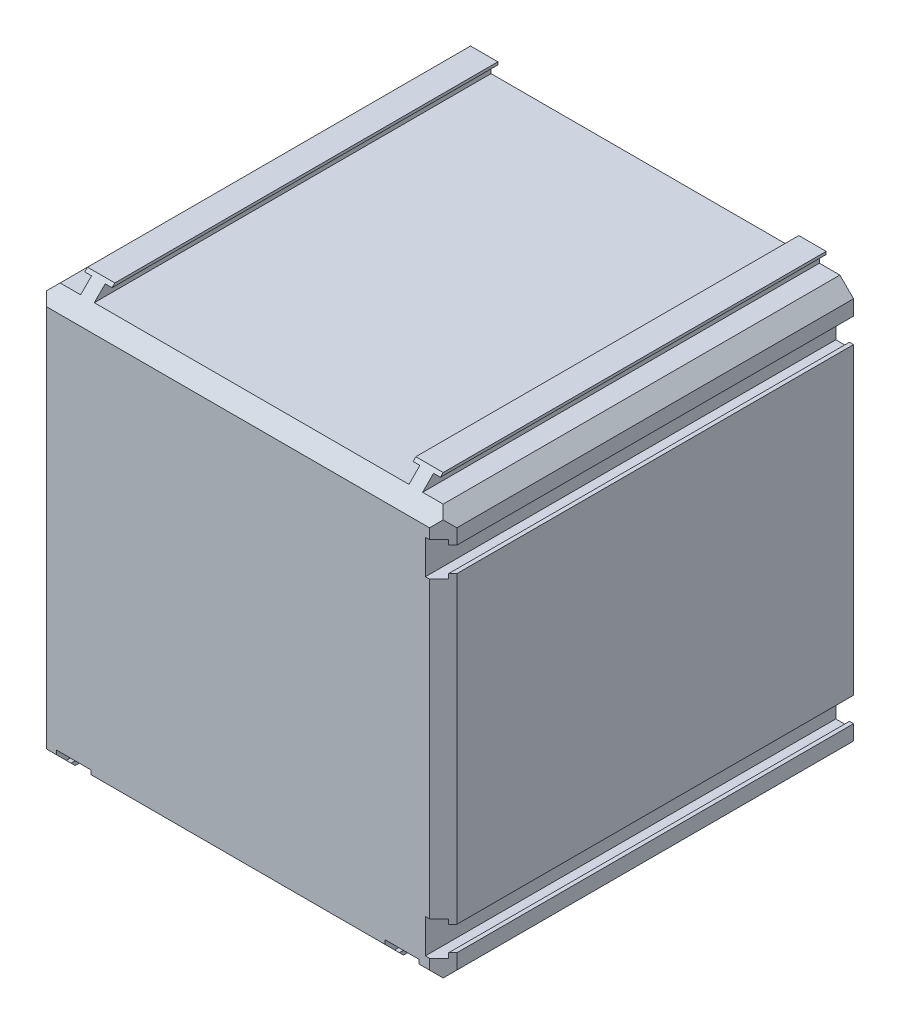
SolidWorks part; units mm, degrees
note: '?' marks a value the reader was unsure of.
ref_plane "前视基准面" through (0, 0, 0) normal (0, 0, 1) x (1, 0, 0)
ref_plane "上视基准面" through (0, 0, 0) normal (0, 1, 0) x (1, 0, 0)
ref_plane "右视基准面" through (0, 0, 0) normal (1, 0, 0) x (0, 0, -1)
sketch "草图1" plane through (0, 0, 0) normal (0, 0, 1) x (1, 0, 0)
  line L46 (-15, -15) -> (15, -15)
  line L65 (-15, -15) -> (-15, 15)
  line L74 (-15, 15) -> (15, 15)
  line L76 (15, -15) -> (15, 15)
  line L77 (-15, -15) -> (15, 15) construction
  line L78 (-15, 15) -> (15, -15) construction
  point P0 (0, 0)
  dimension "D1" = 30
  dimension "D2" = 30
extrude "凸台-拉伸1" add sketch "草图1" along normal blind 30
ref_axis "基准轴1" through (0, 0, 0) along (0, 0, -1)?
chamfer "倒角6" distance 1 angle 45 4 edges at (0, -15, 30) (15, 0, 30) (-15, 0, 30) (0, 15, 30)
sketch "草图6" plane through (0, 0, 0) normal (0, 0, 1) x (1, 0, 0)
  line L0 (-15, 0) -> (15, 0) construction
  line L1 (-12.5, 15) -> (-11.5, 15)
  line L2 (15, 15) -> (-15, 15) construction
  line L3 (-11.5, 15) -> (-11.5, 15.8)
  line L4 (-11.5, 15.8) -> (-11, 15.8)
  line L5 (-11, 15.8) -> (-11, 16)
  line L6 (-11, 16) -> (-13, 16)
  line L7 (-13, 16) -> (-13, 15.8)
  line L8 (-13, 15.8) -> (-12.5, 15.8)
  line L9 (-12.5, 15.8) -> (-12.5, 15)
  line L10 (-15, 15) -> (-15, -15) construction
  line L11 (0, 15) -> (0, -15) construction
  line L12 (-15, -15) -> (15, -15) construction
  line L13 (15, -15) -> (15, 15) construction
  line L15 (-15, 15) -> (15, 15) construction
  dimension "D1" = 2
  dimension "D2" = 0.5
  dimension "D3" = 0.5
  dimension "D4" = 0.2
  dimension "D5" = 0.2
  dimension "D6" = 0.8
  dimension "D7" = 2
  dimension "D8" = 0
extrude "凸台-拉伸3" add sketch "草图6" along normal blind 40
mirror "镜向4" about plane through (0, 0, 0) normal (1, 0, 0) of "凸台-拉伸3"
sketch "草图8" plane through (0, 0, 30) normal (0, 0, 1) x (1, 0, 0)
  line L1 (-12.9, -15) -> (-11.1, -15)
  line L2 (-11.1, -15) -> (-11.1, -14.7)
  line L3 (-11.1, -14.7) -> (-10.75, -14.7)
  line L4 (-10.75, -14.7) -> (-10.75, -13.7)
  line L5 (-10.75, -13.7) -> (-13.25, -13.7)
  line L6 (-13.25, -13.7) -> (-13.25, -14.7)
  line L7 (-13.25, -14.7) -> (-12.9, -14.7)
  line L8 (-12.9, -14.7) -> (-12.9, -15)
  line L30 (0, -15) -> (0, 15) construction
  line L31 (-15, -15) -> (15, -15) construction
  line L144 (-12, 16) -> (-12, -15) construction
  line L146 (15, -15) -> (-15, -15) construction
  point P53 (0, 0)
  point P54 (-12, -15)
  dimension "D1" = 2.5
  dimension "D4" = 1
  dimension "D5" = 1
  dimension "D6" = 0.3
  dimension "D7" = 1.8
pattern_circular "阵列(圆周)8" count 2 over 360 about axis through (0, 0, 0) along (0, 0, -1) of "凸台-拉伸3", "镜向4"
sketch "草图16" plane through (-22, 0, 22) normal (-0.7071, 0, 0.7071) x (0.7071, 0, 0.7071)
  line L1 (4.6388, 19.2844) -> (17.1885, 19.2844)
  line L2 (4.6388, 19.2844) -> (4.6388, -16.3134)
  line L3 (4.6388, -16.3134) -> (17.1885, -16.3134)
  line L4 (17.1885, 19.2844) -> (17.1885, -16.3134)
extrude "切除-拉伸8" cut sketch "草图16" along direction (0, 0, -1) on the side of the normal blind 50 contours L1 L4 L3 L2
sketch "草图17" plane through (0, 22, 22) normal (0, 0.7071, 0.7071) x (1, 0, 0)
  line L1 (-25.1215, 3.7632) -> (20.9983, 3.7632)
  line L2 (-25.1215, 3.7632) -> (-25.1215, -21.3268)
  line L3 (-25.1215, -21.3268) -> (20.9983, -21.3268)
  line L4 (20.9983, 3.7632) -> (20.9983, -21.3268)
extrude "切除-拉伸10" cut sketch "草图17" along direction (0, 0, -1) on the side of the normal blind 50 contours L1 L4 L3 L2
extrude "切除-拉伸2" cut sketch "草图8" against normal blind 30
mirror "镜向1" about plane through (0, 0, 0) normal (1, 0, 0) of "切除-拉伸2"
pattern_circular "阵列(圆周)1" count 2 every 270 about axis through (0, 0, 0) along (0, 0, 1) of "切除-拉伸2", "镜向1"
chamfer "倒角5" distance 1 angle 45 4 edges at (-15, -15, 14.5) (15, -15, 14.5) (15, 15, 14.5) (-15, 15, 14.5)
sketch "草图2" plane through (0, 0, 0) normal (0, 0, -1) x (-1, 0, 0)
  line L12 (-11.5, 15) -> (11.5, 15) construction
  line L13 (-13, 13) -> (13, 13)
  line L14 (-13, 13) -> (-13, -13)
  line L15 (-13, -13) -> (13, -13)
  line L16 (13, 13) -> (13, -13)
  dimension "D1" = 2
extrude "切除-拉伸1" cut sketch "草图2" against normal blind 28
fillet "圆角1" radius 2 2 edges at (-13, -13, 14) (13, -13, 14)
chamfer "倒角1" distance 1.5 angle 45 2 edges at (-13, 13, 14) (13, 13, 14)
sketch "草图9" plane through (0, 0, 0) normal (0, 0, -1) x (-1, 0, 0)
  line L0 (12.3971, 14.2) -> (13.8, 14.2)
  line L1 (14.2, 13.8) -> (14.2, 12.3971)
  line L2 (13.5172, 12.1142) -> (12.1142, 13.5172)
  line L3 (12.5, 15) -> (14, 15) construction
  line L4 (15, 14) -> (15, 12.5) construction
  line L6 (11.5, 13) -> (13, 11.5) construction
  arc A0 (12.1142, 13.5172) -> (12.3971, 14.2) centre (12.3971, 13.8) cw
  arc A1 (14.2, 12.3971) -> (13.5172, 12.1142) centre (13.8, 12.3971) cw
  arc A2 (13.8, 14.2) -> (14.2, 13.8) centre (13.8, 13.8) cw
  dimension "D4" = 0.4
  dimension "D5" = 0.4
  dimension "D6" = 0.4
  dimension "D1" = 0.8
  dimension "D2" = 0.8
  dimension "D3" = 0.8
extrude "切除-拉伸3" cut sketch "草图9" against normal blind 25
sketch "草图12" plane through (0, 0, 0) normal (0, 0, -1) x (-1, 0, 0)
  line L1 (-5, -15) -> (5, -15)
  line L2 (-5, -15) -> (-5, -13)
  line L3 (-5, -13) -> (5, -13)
  line L4 (5, -15) -> (5, -13)
  line L7 (-11, -13) -> (11, -13) construction
  point P8 (0, -13)
  dimension "D1" = 10
extrude "凸台-拉伸6" add sketch "草图12" along normal blind 2
sketch "草图13" plane through (-5, 0, 0) normal (-1, 0, 0) x (0, 0, 1)
  line L0 (-2, -15) -> (-2, -13) construction
  line L2 (-2, -15) -> (0, -15) construction
  circle A0 centre (-1, -14) radius 0.5
  dimension "D1" = 1
  dimension "D2" = 1
  dimension "D3" = 1
extrude "切除-拉伸6" cut sketch "草图13" against normal through all
sketch "草图14" plane through (0, 0, -2) normal (0, 0, -1) x (-1, 0, 0)
  line L0 (-5, -13) -> (-5, -15) construction
  line L1 (-5, -13.75) -> (-4.5, -13.75)
  line L2 (-5, -13.75) -> (-5, -14.25)
  line L3 (-5, -14.25) -> (-4.5, -14.25)
  line L4 (5, -13.75) -> (5, -14.25)
  line L5 (5, -15) -> (5, -13) construction
  line L6 (5, -13) -> (-5, -13) construction
  line L7 (-5, -15) -> (5, -15) construction
  line L8 (-4.5, -13.75) -> (-4.5, -14.25)
  line L9 (4.5, -14.25) -> (4.5, -13.75)
  line L10 (4.5, -13.75) -> (5, -13.75)
  line L11 (4.5, -14.25) -> (5, -14.25)
  dimension "D1" = 0.75
  dimension "D2" = 0.75
  dimension "D3" = 0.5
  dimension "D4" = 0.5
extrude "切除-拉伸7" cut sketch "草图14" against normal blind 1
chamfer "倒角8" distance 0.5 angle 45 2 edges at (0, -13, -2) (0, -15, -2)
fillet "圆角6" radius 0.3 8 edges at (-4.75, -14.25, -1.433) (-4.75, -13.75, -1.433) (-4.75, -14.25, -2) (-4.75, -13.75, -2) (4.75, -14.25, -1.433) (4.75, -14.25, -2) (4.75, -13.75, -2) (4.75, -13.75, -1.433)
